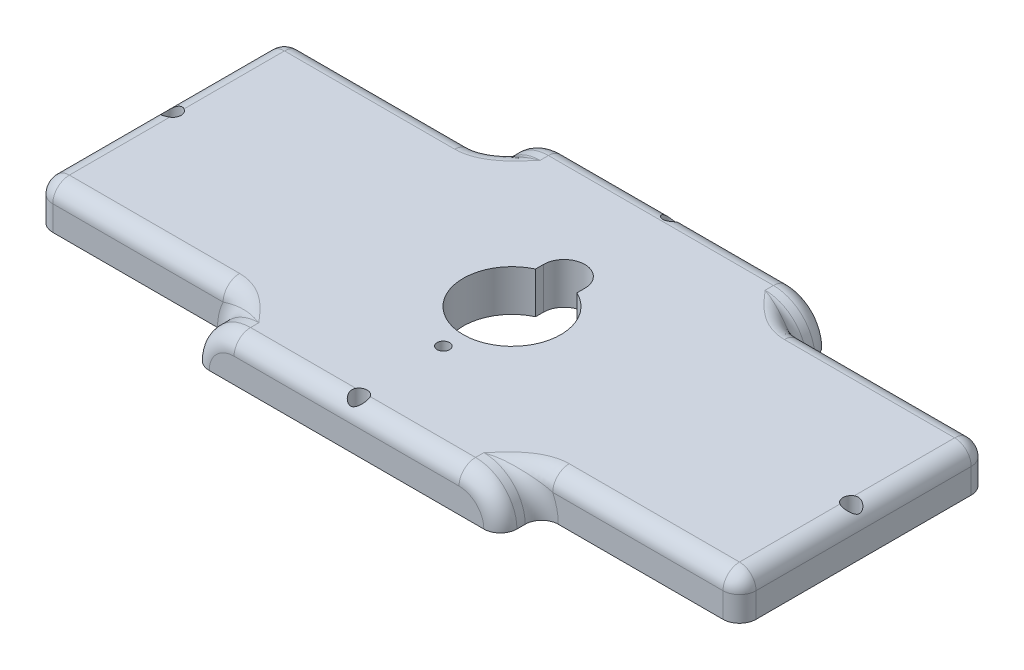
SolidWorks part; units mm, degrees
note: The reader was unsure of these and kept them because the rebuilt part matched: shared geometry of "Croquis8<5>".
ref_plane "Alzado" through (0, 0, 0) normal (0, 0, 1) x (1, 0, 0)
ref_plane "Planta" through (0, 0, 0) normal (0, 1, 0) x (1, 0, 0)
ref_plane "Vista lateral" through (0, 0, 0) normal (1, 0, 0) x (0, 0, -1)
sketch "Croquis1" plane through (0, 0, 0) normal (0, 0, 1) x (1, 0, 0)
  line L1 (-42.5, 15) -> (42.5, 15)
  line L2 (-42.5, 15) -> (-42.5, -15)
  line L3 (-42.5, -15) -> (42.5, -15)
  line L4 (42.5, 15) -> (42.5, -15)
  line L5 (-42.5, 15) -> (42.5, 15)
  line L6 (-42.5, 15) -> (-42.5, 11)
  line L8 (42.5, 15) -> (42.5, 11)
  line L9 (42.5, -15) -> (-42.5, -15)
  line L10 (42.5, -15) -> (42.5, -11)
  line L11 (42.5, -11) -> (-42.5, -11)
  line L12 (-42.5, -15) -> (-42.5, -11)
  line L14 (-42.5, 11) -> (-42.5, -11)
  line L15 (-42.5, -11) -> (-38.5, -11)
  line L16 (-38.5, 15) -> (-38.5, -11)
  line L18 (42.5, 11) -> (42.5, -11)
  line L19 (42.5, -11) -> (38.5, -11)
  line L20 (38.5, 15) -> (38.5, -11)
  point P4 (0, 15)
  point P6 (42.5, 0)
  dimension "D1" = 85
  dimension "D2" = 30
  dimension "D3" = 4
  dimension "D4" = 4
  dimension "D5" = 4
  dimension "D6" = 4
  dimension "D7" = 4
extrude "Saliente-Extruir1" add sketch "Croquis1" along normal mid plane 30 contours L1 L20 L11 L4 | L4 L11 L2 L3 | L16 L1 L2 L11 | L20 L5 L16 L11
fillet "Redondeo3" radius 5 4 edges at (0, 15, -15) (0, 15, 15) (0, -15, -15) (0, -15, 15)
sketch "Croquis2" plane through (0, 0, 0) normal (0, 0, 1) x (1, 0, 0)
  line L7 (-13.5961, 20) -> (13.5961, 20)
  line L8 (18.4468, 13.7873) -> (10.9468, -16.2127)
  line L9 (6.0961, -20) -> (-6.0961, -20)
  line L10 (-10.9468, -16.2127) -> (-18.4468, 13.7873)
  line L11 (-42.5, -15) -> (42.5, -15) construction
  line L12 (-42.5, 15) -> (42.5, 15) construction
  arc A4 (10.9468, -16.2127) -> (6.0961, -20) centre (6.0961, -15) cw
  arc A5 (-6.0961, -20) -> (-10.9468, -16.2127) centre (-6.0961, -15) cw
  arc A6 (13.5961, 20) -> (18.4468, 13.7873) centre (13.5961, 15) cw
  arc A7 (-13.5961, 20) -> (-18.4468, 13.7873) centre (-13.5961, 15) ccw
  point P2 (0, -20)
  point P10 (0, 20)
  point P13 (10, -20)
  point P16 (-10, -20)
  point P19 (20, 20)
  point P23 (-20, 20)
  dimension "D3" = 20
  dimension "D5" = 5
  dimension "D1" = 5
  dimension "D2" = 5
  dimension "D4" = 40
extrude "Saliente-Extruir4" add sketch "Croquis2" along normal mid plane 40
sketch "Croquis5" plane through (0, 0, 0) normal (1, 0, 0) x (0, 0, -1)
  line L1 (-20, -20) -> (20, -20)
  line L2 (-20, -20) -> (-20, 15)
  line L3 (-20, 15) -> (20, 15)
  line L4 (20, -20) -> (20, 15)
  line L5 (-10, 15) -> (10, 15) construction
sketch "Croquis6" plane through (42.5, 0, 0) normal (1, 0, 0) x (0, 0, -1)
  line L0 (10, 15) -> (-10, 15) construction
  line L1 (-15, 15) -> (15, 15)
  line L2 (-15, 15) -> (-15, 16)
  line L3 (-12, 19) -> (12, 19)
  line L4 (15, 15) -> (15, 16)
  arc A0 (12, 19) -> (15, 16) centre (12, 16) cw
  arc A1 (-15, 16) -> (-12, 19) centre (-12, 16) cw
  point P5 (0, 19)
  point P11 (-15, 19)
  dimension "D2" = 3
  dimension "D1" = 4
  dimension "D3" = 30
extrude "Saliente-Extruir5" add sketch "Croquis6" against normal up to next
extrude "Cortar-Extruir2" cut sketch "Croquis5" against normal through all both and the other way through all
mirror "Simetría1" about plane through (0, 0, 0) normal (1, 0, 0) of "Saliente-Extruir5"
sketch "Croquis7" plane through (0, 0, 0) normal (0, 1, 0) x (1, 0, 0)
  line L0 (-42.5, 12) -> (-42.5, -12) construction
  line L2 (42.5, 12) -> (42.5, -12) construction
  line L3 (13.5961, -20) -> (-13.5961, -20) construction
  circle A0 centre (-41, 0) radius 1
  circle A1 centre (0, -18.5) radius 1
  circle A2 centre (41, 0) radius 1
  point P16 (0, -20)
  point P17 (42.5, 0)
  dimension "D1" = 1.5
  dimension "D3" = 1.5
  dimension "D4" = 1.5
  dimension "D5" = 2
extrude "Cortar-Extruir3" cut sketch "Croquis7" against normal through all both and the other way through all
sketch "Croquis8" plane through (0, 20, 0) normal (0, 1, 0) x (1, 0, 0)
  line L0 (2.5, 6.3) -> (2.5, 5.3442)
  line L1 (-2.5, 6.3) -> (-2.5, 5.3442)
  line L2 (0, -5.9) -> (0, -8.3) construction
  line L3 (0, 16.6) -> (0, 19) construction
  line L4 (-13.5961, -20) -> (-13.5961, 20) construction
  line L8 (5.9, -10.6) -> (-5.9, -10.6)
  line L9 (5.9, -10.6) -> (5.9, -5.9)
  line L10 (5.9, -5.9) -> (-5.9, -5.9)
  line L11 (-5.9, -10.6) -> (-5.9, -5.9)
  line L19 (0, 8.8) -> (0, 16.6) construction
  arc A0 (-2.5, 5.3442) -> (2.5, 5.3442) centre (0, 0) ccw
  arc A1 (2.5, 6.3) -> (-2.5, 6.3) centre (0, 6.3) ccw
  circle A2 centre (0, -8.3) radius 0.75
  circle A5 centre (0, 19) radius 0.75
  point P15 (-13.5961, 0)
  point P33 (0, -10.6)
  dimension "D1" = 11.8
  dimension "D2" = 2.4
  dimension "D3" = 8.8
  dimension "D5" = 1.5
  dimension "D6" = 2.5
  dimension "D4" = 2.4
  dimension "D7" = 11.8
  dimension "D8" = 4.7
  dimension "D9" = 7.8
extrude "Saliente-Extruir6" add sketch "Croquis8" against normal blind 4.3 from surface at -5 contours L11 L8 L9 L10 A2 starting at face at (-41, 15, -1)
extrude "Cortar-Extruir4" cut sketch "Croquis8<5>" against normal through all both and the other way through all
sketch "Croquis8<5>" plane through (0, 20, 0) normal (0, 1, 0) x (1, 0, 0) same geometry as "Croquis8"
fillet "Redondeo4" radius 5 3 edges at (0, 15, 10.6) (5.9, 15, 8.25) (-5.9, 15, 8.25)
fillet "Redondeo5" radius 1 4 edges at (0, 10.7, 5.9) (0, 10.7, 10.6) (-5.9, 10.7, 8.25) (5.9, 10.7, 8.25)
fillet "Redondeo6" radius 2 6 edges at (17.1317, 18.5355, -20) (0, 20, -20) (17.1317, 18.5355, 20) (0, 20, 20) (-17.1317, 18.5355, -20) (-17.1317, 18.5355, 20)
sketch "Croquis9" plane through (42.5, 0, 0) normal (1, 0, 0) x (0, 0, -1)
  line L0 (-15, 16) -> (-15, 20)
  line L1 (-18, 20) -> (18, 20) construction
  line L2 (-15, 20) -> (15, 20)
  line L3 (15, 20) -> (15, 16)
  line L4 (-15, 16) -> (15, 16)
extrude "Saliente-Extruir7" add sketch "Croquis9" against normal up to next
fillet "Redondeo7" radius 2 7 edges at (42.5, 17.5, -15) (42.5, 17.5, 15) (28.0481, 20, 15) (28.0481, 20, -15) (42.5, 20, 0) (17.1317, 18.5355, -15) (17.1317, 18.5355, 15)
mirror "Simetría2" about plane through (0, 0, 0) normal (1, 0, 0) of "Saliente-Extruir7"
fillet "Redondeo8" radius 2 7 edges at (-17.1317, 18.5355, 15) (-17.1317, 18.5355, -15) (-42.5, 17.5, -15) (-42.5, 17.5, 15) (-28.0481, 20, -15) (-42.5, 20, 0) (-28.0481, 20, 15)
sketch "Croquis10" plane through (0, 15, 0) normal (0, -1, 0) x (1, 0, 0)
  line L12 (-42.5, 13) -> (-42.5, -13)
  line L13 (-40.5, -15) -> (-20.5961, -15)
  line L14 (-18.5961, -17) -> (-18.5961, -18)
  line L15 (-16.5961, -20) -> (16.5961, -20)
  line L16 (18.5961, -18) -> (18.5961, -17)
  line L17 (20.5961, -15) -> (40.5, -15)
  line L18 (42.5, -13) -> (42.5, 13)
  line L19 (40.5, 15) -> (20.5961, 15)
  line L20 (18.5961, 17) -> (18.5961, 18)
  line L21 (16.5961, 20) -> (-16.5961, 20)
  line L22 (-18.5961, 18) -> (-18.5961, 17)
  line L23 (-20.5961, 15) -> (-40.5, 15)
  line L24 (-42.5, 13) -> (-42.5, -13)
  line L25 (-40.5, -15) -> (-20.5961, -15)
  line L26 (-18.5961, -17) -> (-18.5961, -18)
  line L27 (-16.5961, -20) -> (16.5961, -20)
  line L28 (18.5961, -18) -> (18.5961, -17)
  line L29 (20.5961, -15) -> (40.5, -15)
  line L30 (42.5, -13) -> (42.5, 13)
  line L31 (40.5, 15) -> (20.5961, 15)
  line L32 (18.5961, 17) -> (18.5961, 18)
  line L33 (16.5961, 20) -> (-16.5961, 20)
  line L34 (-18.5961, 18) -> (-18.5961, 17)
  line L35 (-20.5961, 15) -> (-40.5, 15)
  arc A12 (-42.5, -13) -> (-40.5, -15) centre (-40.5, -13) ccw
  arc A13 (-18.5961, -17) -> (-20.5961, -15) centre (-20.5961, -17) ccw
  arc A14 (-18.5961, -18) -> (-16.5961, -20) centre (-16.5961, -18) ccw
  arc A15 (16.5961, -20) -> (18.5961, -18) centre (16.5961, -18) ccw
  arc A16 (20.5961, -15) -> (18.5961, -17) centre (20.5961, -17) ccw
  arc A17 (40.5, -15) -> (42.5, -13) centre (40.5, -13) ccw
  arc A18 (42.5, 13) -> (40.5, 15) centre (40.5, 13) ccw
  arc A19 (18.5961, 17) -> (20.5961, 15) centre (20.5961, 17) ccw
  arc A20 (18.5961, 18) -> (16.5961, 20) centre (16.5961, 18) ccw
  arc A21 (-16.5961, 20) -> (-18.5961, 18) centre (-16.5961, 18) ccw
  arc A22 (-20.5961, 15) -> (-18.5961, 17) centre (-20.5961, 17) ccw
  arc A23 (-40.5, 15) -> (-42.5, 13) centre (-40.5, 13) ccw
  arc A24 (-42.5, -13) -> (-40.5, -15) centre (-40.5, -13) ccw
  arc A25 (-18.5961, -17) -> (-20.5961, -15) centre (-20.5961, -17) ccw
  arc A26 (-18.5961, -18) -> (-16.5961, -20) centre (-16.5961, -18) ccw
  arc A27 (16.5961, -20) -> (18.5961, -18) centre (16.5961, -18) ccw
  arc A28 (20.5961, -15) -> (18.5961, -17) centre (20.5961, -17) ccw
  arc A29 (40.5, -15) -> (42.5, -13) centre (40.5, -13) ccw
  arc A30 (42.5, 13) -> (40.5, 15) centre (40.5, 13) ccw
  arc A31 (18.5961, 17) -> (20.5961, 15) centre (20.5961, 17) ccw
  arc A32 (18.5961, 18) -> (16.5961, 20) centre (16.5961, 18) ccw
  arc A33 (-16.5961, 20) -> (-18.5961, 18) centre (-16.5961, 18) ccw
  arc A34 (-20.5961, 15) -> (-18.5961, 17) centre (-20.5961, 17) ccw
  arc A35 (-40.5, 15) -> (-42.5, 13) centre (-40.5, 13) ccw
  circle M36 centre (-41, 0) radius 1
  circle M38 centre (41, 0) radius 1
  dimension "D1" = 0
extrude "Cortar-Extruir5" cut sketch "Croquis10" against normal up to next contours M36 | M38
